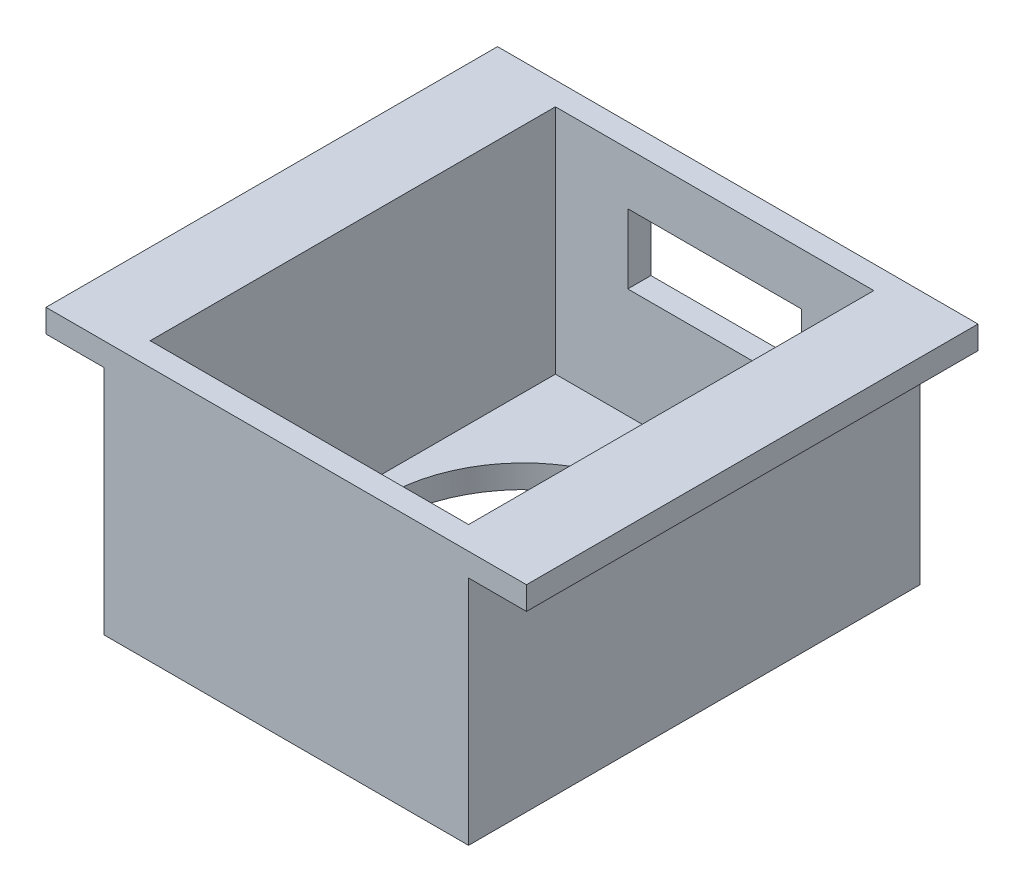
SolidWorks part; units mm, degrees
ref_plane "Front Plane" through (0, 0, 0) normal (0, 0, 1) x (1, 0, 0)
ref_plane "Top Plane" through (0, 0, 0) normal (0, 1, 0) x (1, 0, 0)
ref_plane "Right Plane" through (0, 0, 0) normal (1, 0, 0) x (0, 0, -1)
sketch "Sketch2" plane through (0, 0, 0) normal (0, 0, 1) x (1, 0, 0)
  line L0 (0, 0) -> (7, 0)
  line L1 (7, 0) -> (7, -20)
  line L2 (7, -20) -> (34.5, -20)
  line L3 (34.5, -20) -> (34.5, 0)
  line L4 (34.5, 0) -> (41.5, 0)
  line L5 (0, -2) -> (5, -2)
  line L6 (5, -2) -> (5, -22)
  line L7 (5, -22) -> (36.5, -22)
  line L8 (36.5, -22) -> (36.5, -2)
  line L9 (36.5, -2) -> (41.5, -2)
  line L10 (0, -2) -> (0, 0)
  line L11 (41.5, 0) -> (41.5, -2)
  dimension "D1" = 2
extrude "Boss-Extrude1" add sketch "Sketch2" along normal blind 37
sketch "Sketch3" plane through (0, -22, 0) normal (0, -1, 0) x (1, 0, 0)
  line L1 (36.5, 0) -> (36.5, 37)
  circle A0 centre (20.75, 18.5) radius 12
sketch "Sketch5" plane through (0, 0, 37) normal (0, 0, 1) x (1, 0, 0)
  line L0 (0, 0) -> (41.5, 0)
  line L1 (41.5, 0) -> (41.5, -2)
  line L2 (41.5, -2) -> (36.5, -2)
  line L3 (36.5, -2) -> (36.5, -22)
  line L4 (36.5, -22) -> (5, -22)
  line L5 (5, -22) -> (5, -2)
  line L6 (5, -2) -> (0, -2)
  line L7 (0, -2) -> (0, 0)
extrude "Boss-Extrude2" add sketch "Sketch5" along normal blind 2
extrude "Boss-Extrude3" add sketch "Sketch5<2>" against normal blind 2 from offset 35 offset against normal yes
sketch "Sketch5<2>" plane through (0, 0, 37) normal (0, 0, 1) x (1, 0, 0) same geometry as "Sketch5"
sketch "Sketch6" plane through (0, 0, 0) normal (0, 0, -1) x (-1, 0, 0)
  line L3 (-20.75, -9) -> (-14.75, -9)
  line L4 (-14.75, -9) -> (-14.75, -6)
  line L5 (-14.75, -6) -> (-26.75, -6)
  line L6 (-26.75, -6) -> (-26.75, -9)
  line L7 (-26.75, -9) -> (-20.75, -9)
extrude "Cut-Extrude2" cut sketch "Sketch6" against normal blind 2
sketch "Sketch8" plane through (0, 0, 0) normal (0, 0, -1) x (-1, 0, 0)
  line L0 (-28.25, -4.5) -> (-28.25, -10.5)
  line L1 (-26.75, -6) -> (-14.75, -6)
  line L2 (-26.75, -6) -> (-26.75, -9)
  line L3 (-26.75, -9) -> (-14.75, -9)
  line L4 (-14.75, -6) -> (-14.75, -9)
  line L5 (-28.25, -10.5) -> (-13.25, -10.5)
  line L6 (-13.25, -4.5) -> (-13.25, -10.5)
  line L7 (-28.25, -4.5) -> (-13.25, -4.5)
  dimension "D1" = 1.5
extrude "Cut-Extrude3" cut sketch "Sketch8" against normal blind 10
extrude "Cut-Extrude4" cut sketch "Sketch3" against normal blind 10 contours A0 region at (20.75, -22, 18.5)
